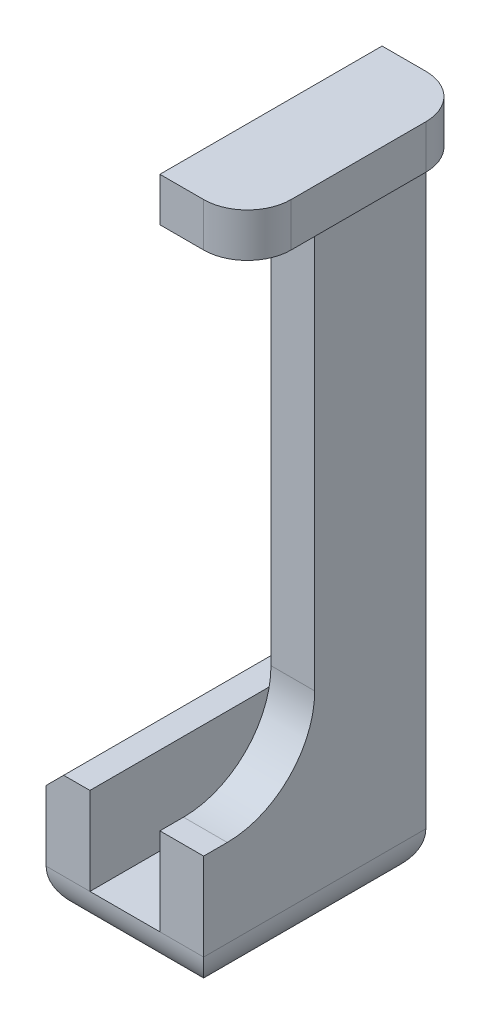
SolidWorks part; units mm, degrees
ref_plane "Front Plane" through (0, 0, 0) normal (0, 0, 1) x (1, 0, 0)
ref_plane "Top Plane" through (0, 0, 0) normal (0, 1, 0) x (1, 0, 0)
ref_plane "Right Plane" through (0, 0, 0) normal (1, 0, 0) x (0, 0, -1)
sketch "Sketch1" plane through (0, 0, 0) normal (0, 0, 1) x (1, 0, 0)
  line L0 (0, 0) -> (-8, 0)
  line L1 (-8, 0) -> (-8, 10)
  line L2 (-8, 10) -> (-13, 10)
  line L3 (-13, 10) -> (-13, -5)
  line L4 (-13, -5) -> (5, -5)
  line L5 (5, -5) -> (5, 70)
  line L6 (5, 70) -> (10, 70)
  line L7 (10, 70) -> (10, 75)
  line L8 (10, 75) -> (0, 75)
  line L9 (0, 75) -> (0, 0)
  dimension "D1" = 8
  dimension "D2" = 5
  dimension "D3" = 5
  dimension "D4" = 10
  dimension "D5" = 5
  dimension "D6" = 75
  dimension "D7" = 5
  dimension "D8" = 5
extrude "Boss-Extrude1" add sketch "Sketch1" along normal blind 12.7
sketch "Sketch2" plane through (0, 0, 12.7) normal (0, 0, 1) x (1, 0, 0)
  line L0 (0, 10) -> (5, 10)
  line L1 (5, 70) -> (0, 70)
  line L10 (0, 75) -> (0, 0)
  line L11 (0, 0) -> (-8, 0)
  line L12 (-8, 0) -> (-8, 10)
  line L13 (-8, 10) -> (-13, 10)
  line L14 (-13, 10) -> (-13, -5)
  line L15 (-13, -5) -> (5, -5)
  line L16 (5, -5) -> (5, 70)
  line L17 (5, 70) -> (10, 70)
  line L18 (10, 70) -> (10, 75)
  line L19 (10, 75) -> (0, 75)
  line L20 (0, 75) -> (0, 0)
  line L21 (0, 0) -> (-8, 0)
  line L22 (-8, 0) -> (-8, 10)
  line L23 (-8, 10) -> (-13, 10)
  line L24 (-13, 10) -> (-13, -5)
  line L25 (-13, -5) -> (5, -5)
  line L26 (5, -5) -> (5, 70)
  line L27 (5, 70) -> (10, 70)
  line L28 (10, 70) -> (10, 75)
  line L29 (10, 75) -> (0, 75)
  line M11 (0, 75) -> (0, 0)
  line M12 (0, 0) -> (-8, 0)
  line M13 (-8, 0) -> (-8, 10)
  line M14 (-8, 10) -> (-13, 10)
  line M15 (-13, 10) -> (-13, -5)
  line M16 (-13, -5) -> (5, -5)
  line M17 (5, -5) -> (5, 70)
  line M18 (5, 70) -> (10, 70)
  line M19 (10, 70) -> (10, 75)
  line M20 (10, 75) -> (0, 75)
  dimension "D1" = 0
extrude "Boss-Extrude2" add sketch "Sketch2" along normal blind 12.7 contours L0 M11 M12 M13 M14 M15 M16 M17 | L1 M18 M19 M20 M11 region at (2.5, 9.7657, 12.7) region at (5, 72.5, 12.7)
fillet "Fillet1" radius 10 1 edges at (2.5, 10, 12.7)
fillet "Fillet2" radius 5 7 edges at (-13, -5, 12.7) (-4, -5, 25.4) (5, -5, 12.7) (-4, -5, 0) (10, 72.5, 0) (10, 72.5, 25.4) (2.5, 70, 12.7)
chamfer "Chamfer2" distance 2 angle 45 1 edges at (-13, 10, 12.7)
